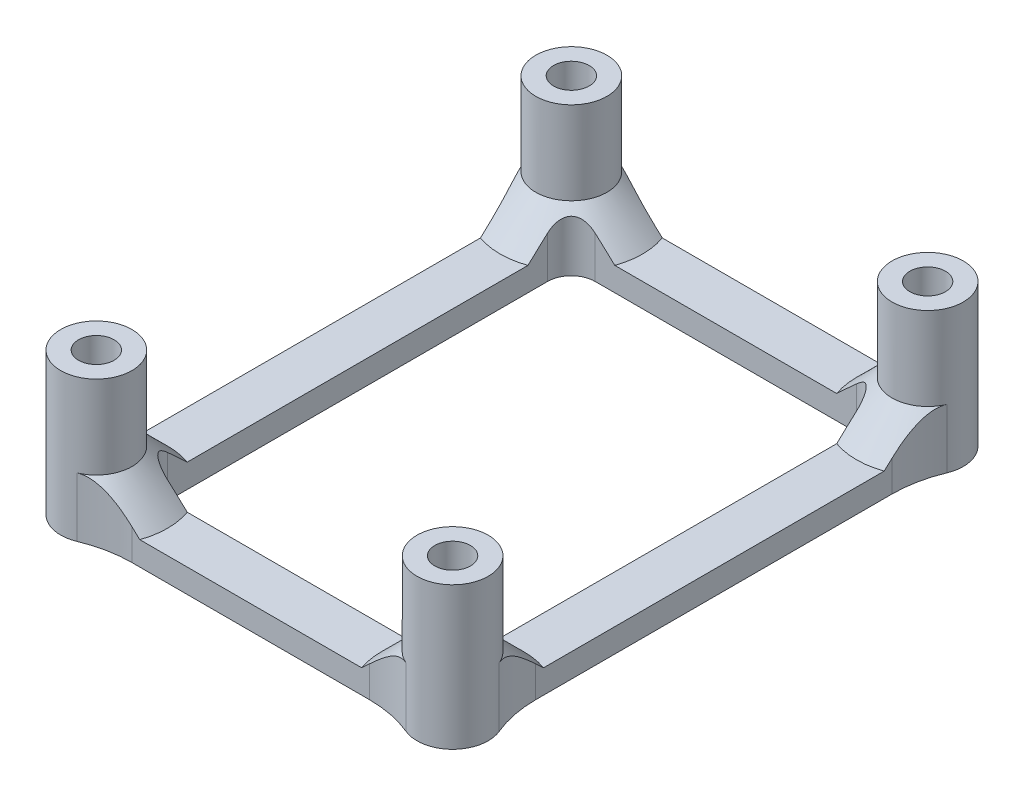
SolidWorks part; units mm, degrees
material "ABS"
ref_plane "Front Plane" through (0, 0, 0) normal (0, 0, 1) x (1, 0, 0)
ref_plane "Top Plane" through (0, 0, 0) normal (0, 1, 0) x (1, 0, 0)
ref_plane "Right Plane" through (0, 0, 0) normal (1, 0, 0) x (0, 0, -1)
sketch "Sketch1" plane through (0, 0, 0) normal (0, 1, 0) x (1, 0, 0)
  line L0 (-15, -20) -> (15, -20) construction
  line L1 (-15, -20) -> (-15, 20) construction
  line L2 (15, -20) -> (15, 20) construction
  line L3 (-15, 20) -> (15, 20) construction
  line L4 (-15, -20) -> (15, 20) construction
  line L5 (15, -20) -> (-15, 20) construction
  line L6 (-11, 18) -> (11, 18)
  line L7 (13, -16) -> (13, 16)
  line L8 (-11, -18) -> (11, -18)
  line L9 (-13, -16) -> (-13, 16)
  line L10 (-12.7639, 22) -> (12.7639, 22)
  line L11 (17, -17.7639) -> (17, 17.7639)
  line L12 (-12.7639, -22) -> (12.7639, -22)
  line L13 (-17, -17.7639) -> (-17, 17.7639)
  line L14 (13, -18) -> (13, 18) construction
  line L15 (-13, -18) -> (13, -18) construction
  line L16 (-13, -18) -> (-13, 18) construction
  line L17 (-13, 18) -> (13, 18) construction
  line L18 (-17, -22) -> (17, -22) construction
  line L19 (-17, -22) -> (-17, 22) construction
  line L20 (17, -22) -> (17, 22) construction
  line L21 (-17, 22) -> (17, 22) construction
  circle A0 centre (-15, 20) radius 1.5
  circle A1 centre (15, 20) radius 1.5
  circle A2 centre (15, -20) radius 1.5
  circle A3 centre (-15, -20) radius 1.5
  arc A5 (17, 17.7639) -> (12.7639, 22) centre (15, 20) ccw
  arc A6 (12.7639, -22) -> (17, -17.7639) centre (15, -20) ccw
  arc A7 (-17, -17.7639) -> (-12.7639, -22) centre (-15, -20) ccw
  arc A8 (13, -16) -> (11, -18) centre (11, -16) cw
  arc A9 (-13, -16) -> (-11, -18) centre (-11, -16) ccw
  arc A10 (11, 18) -> (13, 16) centre (11, 16) cw
  arc A11 (-13, 16) -> (-11, 18) centre (-11, 16) cw
  arc A12 (-12.7639, 22) -> (-17, 17.7639) centre (-15, 20) ccw
  point P1 (0, 0)
  dimension "D1" = 3
  dimension "D6" = 3
  dimension "D7" = 2
  dimension "D2" = 30
  dimension "D3" = 40
  dimension "D4" = 2
  dimension "D5" = 2
extrude "Boss-Extrude1" add sketch "Sketch1" along normal blind 2
fillet "Fillet1" radius 10 8 edges at (12.7639, 1, 22) (-17, 1, 17.7639) (-12.7639, 1, 22) (17, 1, 17.7639) (17, 1, -17.7639) (12.7639, 1, -22) (-12.7639, 1, -22) (-17, 1, -17.7639)
sketch "Sketch2" plane through (0, 2, 0) normal (0, 1, 0) x (1, 0, 0)
  circle A0 centre (15, 20) radius 3
  circle A1 centre (15, 20) radius 1.5
  circle A2 centre (15, -20) radius 1.5
  circle A3 centre (15, -20) radius 3
  circle A4 centre (-15, -20) radius 1.5
  circle A5 centre (-15, -20) radius 3
  circle A6 centre (-15, 20) radius 1.5
  circle A7 centre (-15, 20) radius 3
  arc A8 (17.7692, 18.8462) -> (13.8462, 22.7692) centre (15, 20) ccw construction
  circle A9 centre (15, 20) radius 1.5 construction
extrude "Boss-Extrude2" add sketch "Sketch2" along normal blind 10
chamfer "Chamfer1" distance 3 angle 45 4 edges at (12.8787, 2, -17.8787) (-12.8787, 2, -17.8787) (-12.8787, 2, 17.8787) (12.8787, 2, 17.8787)
